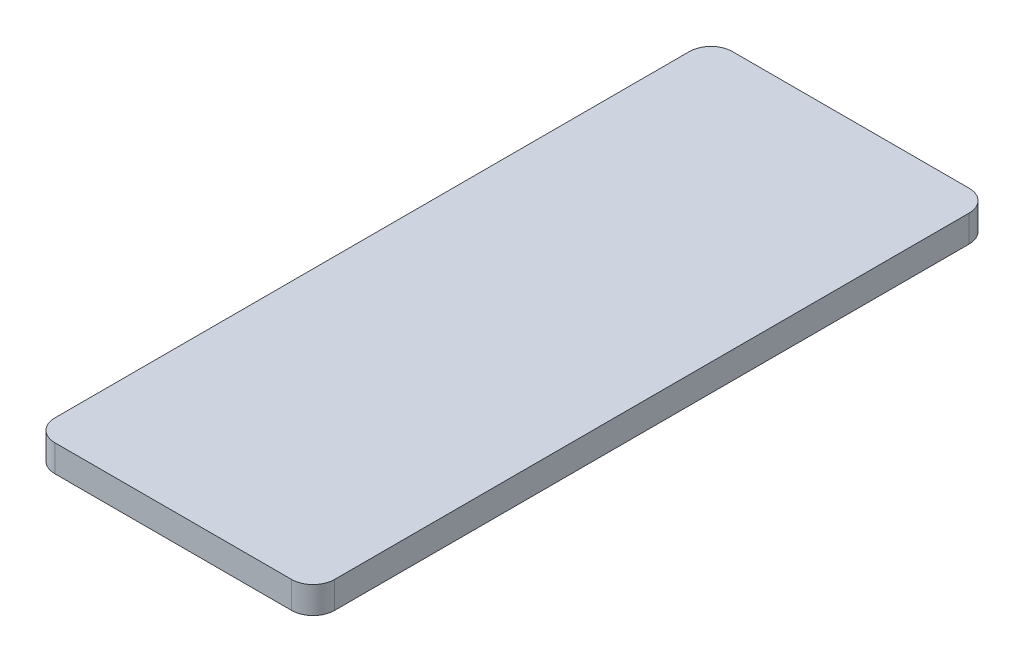
SolidWorks part; units mm, degrees
material "Acrylic (Medium-high impact)"
ref_plane "Front Plane" through (0, 0, 0) normal (0, 0, 1) x (1, 0, 0)
ref_plane "Top Plane" through (0, 0, 0) normal (0, 1, 0) x (1, 0, 0)
ref_plane "Right Plane" through (0, 0, 0) normal (1, 0, 0) x (0, 0, -1)
ref_plane "Plane1" through (0, 0, 0) normal (0, 1, 0) x (1, 0, 0)
sketch "Sketch1" plane through (0, 0, 0) normal (0, 1, 0) x (1, 0, 0)
  line L1 (-26.2811, -23.7838) -> (6.7489, -23.7838)
  line L2 (-26.2811, -23.7838) -> (-26.2811, 56.2162)
  line L3 (-26.2811, 56.2162) -> (6.7489, 56.2162)
  line L4 (6.7489, -23.7838) -> (6.7489, 56.2162)
  dimension "D1" = 80
  dimension "D2" = 33.03
extrude "Boss-Extrude1" add sketch "Sketch1" along normal blind 3.175
fillet "Fillet1" radius 2.54 4 edges at (-26.2811, 1.5875, -56.2162) (6.7489, 1.5875, -56.2162) (6.7489, 1.5875, 23.7838) (-26.2811, 1.5875, 23.7838)
